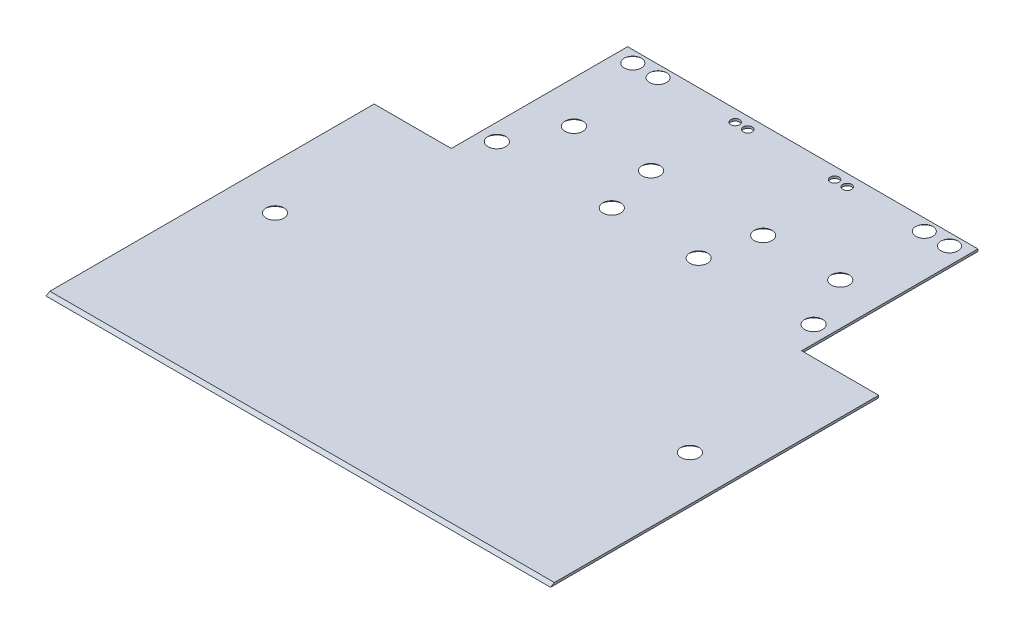
SolidWorks part; units mm, degrees
ref_plane "Alzado" through (0, 0, 0) normal (0, 0, 1) x (1, 0, 0)
ref_plane "Planta" through (0, 0, 0) normal (0, 1, 0) x (1, 0, 0)
ref_plane "Vista lateral" through (0, 0, 0) normal (1, 0, 0) x (0, 0, -1)
sketch "Croquis1" plane through (0, 0, 0) normal (0, 1, 0) x (1, 0, 0)
  line L0 (-62.5, 90) -> (-62.5, 27.08)
  line L1 (90, -90) -> (-90, -90)
  line L2 (90, -90) -> (90, 27.08)
  line L3 (62.5, 90) -> (-62.5, 90)
  line L4 (-90, -90) -> (-90, 27.08)
  line L5 (90, -90) -> (-62.5, 62.5) construction
  line L6 (62.5, 62.5) -> (-90, -90) construction
  line L7 (-62.5, 27.08) -> (-90, 27.08)
  line L8 (0, 90) -> (0, -90) construction
  line L9 (62.5, 27.08) -> (90, 27.08)
  line L10 (62.5, 90) -> (62.5, 27.08)
  point P0 (0, 0)
  dimension "D1" = 125
  dimension "D2" = 180
  dimension "D3" = 27.5
  dimension "D4" = 62.92
  dimension "D5" = 27.5
extrude "Saliente-Extruir1" add sketch "Croquis1" along normal blind 0.8
sketch "Croquis2" plane through (-90, 0, 0) normal (-1, 0, 0) x (0, 0, 1)
  line L0 (90, 0) -> (88.6144, 0.8)
  line L1 (-27.08, 0.8) -> (90, 0.8) construction
  line L2 (88.6144, 0.8) -> (90, 0.8)
  line L3 (90, 0.8) -> (90, 0)
  dimension "D1" = 60
extrude "Cortar-Extruir1" cut sketch "Croquis2" against normal up to next
sketch "Croquis3" plane through (0, 0.8, 0) normal (0, 1, 0) x (1, 0, 0)
  circle A0 centre (74, -24.2793) radius 1.585
extrude "Cortar-Extruir2" cut sketch "Croquis3" against normal up to next
mirror "Simetría1" about plane through (0, 0, 0) normal (1, 0, 0) of "Cortar-Extruir2"
sketch "Croquis4" plane through (0, 0.8, 0) normal (0, 1, 0) x (1, 0, 0)
  circle A0 centre (-56.5, 37.3511) radius 1.585
  circle A1 centre (-15.5, 37.3511) radius 1.585
  circle A2 centre (-15.5, 85.8511) radius 1.585
  circle A3 centre (-56.5, 85.8511) radius 1.585
extrude "Cortar-Extruir3" cut sketch "Croquis4" against normal up to next
sketch "Croquis6" plane through (0, 0.8, 0) normal (0, 1, 0) x (1, 0, 0)
  circle A0 centre (56.5, 85.8511) radius 1.585
  circle A1 centre (15.5, 85.8511) radius 1.585
  circle A2 centre (15.5, 37.3511) radius 1.585
  circle A3 centre (56.5, 37.3511) radius 1.585
extrude "Cortar-Extruir4" cut sketch "Croquis6" against normal up to next
sketch "Croquis7" plane through (0, 0.8, 0) normal (0, 1, 0) x (1, 0, 0)
  circle A0 centre (-20, 85.8511) radius 1.585
  circle A1 centre (-47.5, 85.8511) radius 1.585
  circle A2 centre (-47.5, 55.8511) radius 1.585
  circle A3 centre (-20, 55.8511) radius 1.585
extrude "Cortar-Extruir5" cut sketch "Croquis7" against normal up to next
mirror "Simetría2" about plane through (0, 0, 0) normal (1, 0, 0) of "Cortar-Extruir5"
sketch "Croquis15" plane through (0, 0, 0) normal (0, -1, 0) x (-1, 0, 0)
  circle A0 centre (20, 55.8511) radius 4
  circle A1 centre (15.5, 37.3511) radius 4
  circle A2 centre (56.5, 37.3511) radius 4
  circle A3 centre (47.5, 55.8511) radius 4
  circle A4 centre (56.5, 85.8511) radius 4
  circle A5 centre (47.5, 85.8511) radius 4
  circle A8 centre (74, -24.2793) radius 4
  dimension "D1" = 8
  dimension "D3" = 8
  dimension "D4" = 8
  dimension "D5" = 8
  dimension "D6" = 8
  dimension "D7" = 8
  dimension "D8" = 8
extrude "Cortar-Extruir6" cut sketch "Croquis15" against normal blind 2 draft 50.5
mirror "Simetría3" about plane through (0, 0, 0) normal (1, 0, 0) of "Cortar-Extruir6"
sketch "Croquis13" plane through (0, 0, 0) normal (0, -1, 0) x (-1, 0, 0)
  point P0 (-74, -24.2793)
  point P3 (-56.5, 37.3511)
  point P6 (-47.5, 55.8511)
  point P9 (-20, 55.8511)
  point P12 (-15.5, 37.3511)
  point P15 (15.5, 37.3511)
  point P18 (20, 55.8511)
  point P21 (47.5, 55.8511)
  point P24 (56.5, 37.3511)
  point P27 (74, -24.2793)
hole_wizard "Avellanado para tornillo con cabeza avellanada en cruz de M3.51" positions "Croquis13" profile "Croquis14" countersink size "M3.5" standard "AS" end condition through all
sketch "Croquis14" plane through (74, 0, 24.2793) normal (1, 0, 0) x (0, 0, -1)
  line L0 (0, 0) -> (0, 0.8)
  line L1 (0, 0.8) -> (1.95, 0.8)
  line L2 (1.95, 0.8) -> (1.95, 1.9797)
  line L3 (1.95, 1.9797) -> (4, 0)
  line L5 (4, 0) -> (0, 0)
  line L6 (-1.95, 1.9797) -> (-4, 0) construction
  line L11 (0, -6.35) -> (0, 107.95) construction
  dimension "Diámetro de taladro hasta el siguiente" = 3.9
  dimension "Profundidad de taladro hasta el siguiente" = 0.8
  dimension "Diámetro de avellanado cercano" = 8
  dimension "Ángulo de avellanado cercano" = 92
